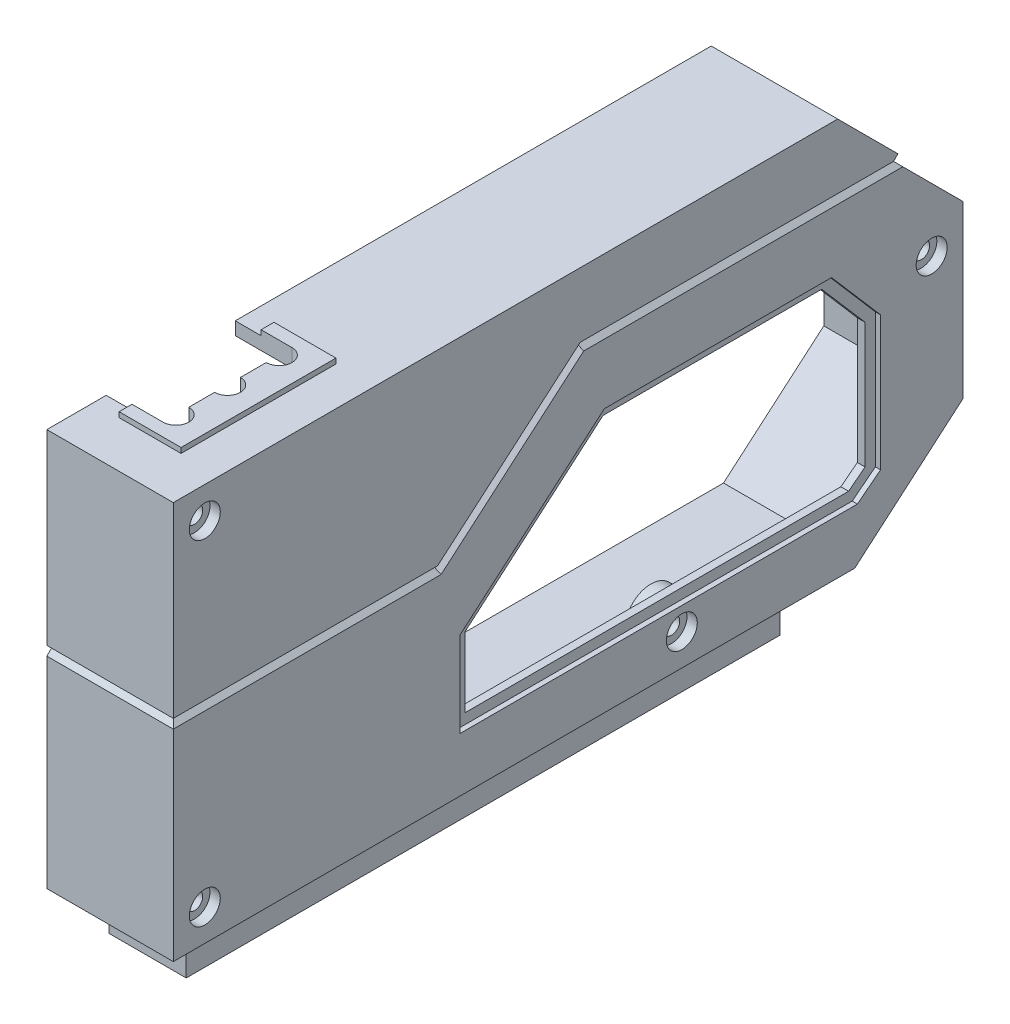
SolidWorks part; units mm, degrees
ref_plane "Front Plane" through (0, 0, 0) normal (0, 0, 1) x (1, 0, 0)
ref_plane "Top Plane" through (0, 0, 0) normal (0, 1, 0) x (1, 0, 0)
ref_plane "Right Plane" through (0, 0, 0) normal (1, 0, 0) x (0, 0, -1)
sketch "Sketch1" plane through (0, 0, 0) normal (1, 0, 0) x (0, 0, -1)
  line L0 (0, 0) -> (0, 77)
  line L1 (0, 77) -> (127, 77)
  line L2 (127, 77) -> (153, 51)
  line L3 (153, 51) -> (153, 18)
  line L4 (153, 18) -> (132, 0)
  line L5 (132, 0) -> (0, 0)
  dimension "D1" = 132
  dimension "D2" = 77
  dimension "D3" = 26
  dimension "D4" = 26
  dimension "D5" = 153
  dimension "D6" = 18
extrude "Base" add sketch "Sketch1" along normal blind 2.5
sketch "Sketch11" plane through (0, 0, 0) normal (-1, 0, 0) x (0, 0, 1)
  line L12 (-131.0752, 2.5) -> (-2.5, 2.5)
  line L13 (-2.5, 2.5) -> (-2.5, 74.5)
  line L14 (-2.5, 74.5) -> (-125.9645, 74.5)
  line L15 (-125.9645, 74.5) -> (-150.5, 49.9645)
  line L16 (-150.5, 49.9645) -> (-150.5, 19.1498)
  line L17 (-150.5, 19.1498) -> (-131.0752, 2.5)
  line L18 (-131.0752, 2.5) -> (-2.5, 2.5)
  line L19 (-2.5, 2.5) -> (-2.5, 74.5)
  line L20 (-2.5, 74.5) -> (-125.9645, 74.5)
  line L21 (-125.9645, 74.5) -> (-150.5, 49.9645)
  line L22 (-150.5, 49.9645) -> (-150.5, 19.1498)
  line L23 (-150.5, 19.1498) -> (-131.0752, 2.5)
  line M7 (-132, 0) -> (0, 0)
  line M8 (0, 0) -> (0, 77)
  line M9 (0, 77) -> (-127, 77)
  line M10 (-127, 77) -> (-153, 51)
  line M11 (-153, 51) -> (-153, 18)
  line M12 (-153, 18) -> (-132, 0)
  dimension "D1" = 2.5
extrude "Boss-Extrude6" add sketch "Sketch11" along normal blind 22 contours L23 L22 L21 L20 L19 L18 M12 M7 M8 M9 M10 M11 region at (0, 10.3005, -141.3853)
ref_plane "Middle" through (-11, 0, 0) normal (1, 0, 0) x (0, 0, -1)
sketch "Sketch17" plane through (0, 77, 0) normal (0, 1, 0) x (1, 0, 0)
  line L5 (-11, -42.35) -> (-11, 42.35) construction
  line L6 (-5, 39) -> (-17, 39)
  line L7 (-5, 39) -> (-5, 9)
  line L8 (-5, 9) -> (-17, 9)
  line L9 (-17, 39) -> (-17, 9)
  line L10 (-5, 39) -> (-17, 9) construction
  line L11 (-5, 9) -> (-17, 39) construction
  line L12 (2.5, 0) -> (-22, 0) construction
  point P0 (-11, 24)
  dimension "D1" = 12
  dimension "D2" = 30
  dimension "D3" = 24
extrude "Boss-Extrude8" add sketch "Sketch17" along normal blind 1
sketch "Sketch13" plane through (0, 78, 0) normal (0, 1, 0) x (1, 0, 0)
  line L0 (-22, 11.5) -> (-11, 11.5)
  line L1 (-22, 0) -> (-22, 127) construction
  line L2 (-11, 16.5) -> (-11, 21.5)
  line L3 (-11, 26.5) -> (-11, 31.5)
  line L4 (-11, 36.5) -> (-22, 36.5)
  line L5 (-22, 36.5) -> (-22, 11.5)
  line L6 (-5, 9) -> (-5, 39) construction
  line L7 (-11, -42.35) -> (-11, 42.35) construction
  arc A0 (-11, 11.5) -> (-11, 16.5) centre (-11, 14) ccw
  arc A1 (-11, 21.5) -> (-11, 26.5) centre (-11, 24) ccw
  arc A2 (-11, 31.5) -> (-11, 36.5) centre (-11, 34) ccw
  point P9 (-5, 24)
  dimension "D1" = 5
  dimension "D4" = 10
  dimension "D5" = 10
extrude "Cut-Extrude2" cut sketch "Sketch13" against normal up to next
sketch "Sketch19" plane through (2.5, 0, 0) normal (1, 0, 0) x (0, 0, -1)
  line L0 (127, 77) -> (128.6971, 77)
  line L1 (128.6971, 77) -> (140.3643, 65.3327)
  line L2 (140.3643, 65.3327) -> (139.5158, 64.4842)
  line L3 (153, 51) -> (127, 77) construction
  line L4 (139.5158, 64.4842) -> (127, 77)
  dimension "D1" = 1.2
  dimension "D2" = 16.5
extrude "Boss-Extrude9" add sketch "Sketch19" against normal up to vertex (24.5 mm away) up to point (-22, 77, -127)
sketch "Sketch20" plane through (0, 102.8485, -102.8485) normal (0, 0.7071, -0.7071) x (-1, 0, 0)
  line L1 (11, 42.35) -> (11, -42.35) construction
  line L2 (2.5, -53.0553) -> (19.5, -53.0553)
  line L3 (2.5, -53.0553) -> (2.5, -44.5553)
  line L4 (2.5, -44.5553) -> (19.5, -44.5553)
  line L5 (19.5, -53.0553) -> (19.5, -44.5553)
  line L6 (2.5, -53.0553) -> (19.5, -44.5553) construction
  line L7 (2.5, -44.5553) -> (19.5, -53.0553) construction
  line L8 (-2.5, -53.0553) -> (-2.5, -36.5553) construction
  line L9 (22, -36.5553) -> (-2.5, -36.5553) construction
  line L10 (22, -53.0553) -> (-2.5, -53.0553) construction
  point P2 (11, -48.8053)
  dimension "D1" = 5
  dimension "D2" = 8
extrude "Cut-Extrude5" cut sketch "Sketch20" against normal up to vertex (1.2 mm away) up to point (2.5, 64.4842, -139.5158)
sketch "Sketch21" plane through (0, 102, -102) normal (0, 0.7071, -0.7071) x (-1, 0, 0)
  line L0 (11, 48.4) -> (11, -48.4) construction
  line L1 (19.5, -44.5553) -> (2.5, -44.5553) construction
  line L2 (11, -48.0053) -> (22, -48.0053)
  line L3 (22, -48.0053) -> (22, -53.1053)
  line L4 (22, -53.0553) -> (22, -72.1249) construction
  line L5 (11, -53.1053) -> (22, -53.1053)
  line L6 (22, 44.5477) -> (22, 46.3155) construction
  arc A0 (11, -48.0053) -> (11, -53.1053) centre (11, -50.5553) ccw
  dimension "D1" = 5.1
  dimension "D2" = 6
extrude "Cut-Extrude6" cut sketch "Sketch21" against normal mid plane 10
sketch "Sketch22" plane through (0, 0, 0) normal (0, -1, 0) x (1, 0, 0)
  line L0 (-11, -42.9) -> (-11, 42.9) construction
  line L1 (-18.5, -8.5) -> (-3.5, -8.5)
  line L2 (-18.5, -8.5) -> (-18.5, -123.5)
  line L3 (-18.5, -123.5) -> (-3.5, -123.5)
  line L4 (-3.5, -8.5) -> (-3.5, -123.5)
  line L5 (-18.5, -8.5) -> (-3.5, -123.5) construction
  line L6 (-18.5, -123.5) -> (-3.5, -8.5) construction
  line L7 (2.5, 0) -> (2.5, -132) construction
  point P0 (-11, -66)
  point P11 (2.5, -66)
  dimension "D1" = 115
  dimension "D2" = 15
extrude "Boss-Extrude10" add sketch "Sketch22" along normal blind 10
sketch "Sketch23" plane through (0, -10, 0) normal (0, -1, 0) x (1, 0, 0)
  line L4 (-18.5, -8.5) -> (-18.5, -123.5) construction
  line L5 (-5.5, -10.5) -> (-16.5, -10.5)
  line L6 (-5.5, -10.5) -> (-5.5, -60.5)
  line L7 (-5.5, -60.5) -> (-16.5, -60.5)
  line L8 (-16.5, -10.5) -> (-16.5, -60.5)
  line L9 (-3.5, -123.5) -> (-3.5, -8.5) construction
  line L10 (-3.5, -8.5) -> (-18.5, -8.5) construction
  dimension "D1" = 2
  dimension "D2" = 2
  dimension "D3" = 2
  dimension "D4" = 50
extrude "Cut-Extrude7" cut sketch "Sketch23" against normal up to next
sketch "Sketch24" plane through (0, -10, 0) normal (0, -1, 0) x (1, 0, 0)
  line L0 (-16.5, -10.5) -> (-16.5, -60.5) construction
  line L1 (-5.5, -60.5) -> (-16.5, -60.5)
  line L2 (-5.5, -60.5) -> (-5.5, -121.5)
  line L3 (-5.5, -121.5) -> (-16.5, -121.5)
  line L4 (-16.5, -60.5) -> (-16.5, -121.5)
  line L5 (-18.5, -123.5) -> (-3.5, -123.5) construction
  dimension "D1" = 2
extrude "Cut-Extrude8" cut sketch "Sketch24" against normal blind 10
sketch "Sketch28" plane through (2.5, 0, 0) normal (1, 0, 0) x (0, 0, -1)
  circle A0 centre (6.1, 70.9) radius 5
  circle A1 centre (146.9, 44.9) radius 5
  circle A2 centre (98.5, 6.1) radius 5
  circle A3 centre (6.1, 6.1) radius 5
  dimension "D9" = 10
  dimension "D1" = 6.1
  dimension "D2" = 6.1
  dimension "D3" = 70.9
  dimension "D4" = 6.1
  dimension "D5" = 98.5
  dimension "D6" = 6.1
  dimension "D7" = 44.9
  dimension "D8" = 146.9
extrude "Boss-Extrude11" add sketch "Sketch28" against normal blind 6
sketch "Sketch29" plane through (2.5, 0, 0) normal (1, 0, 0) x (0, 0, -1)
  circle A0 centre (6.1, 70.9) radius 3
  circle A1 centre (146.9, 44.9) radius 3
  circle A2 centre (98.5, 6.1) radius 3
  circle A3 centre (6.1, 6.1) radius 3
  dimension "D1" = 6
extrude "Cut-Extrude11" cut sketch "Sketch29" against normal blind 2
sketch "Sketch30" plane through (0.5, 0, 0) normal (1, 0, 0) x (0, 0, -1)
  circle A0 centre (6.1, 70.9) radius 1.6
  circle A1 centre (6.1, 6.1) radius 1.6
  circle A2 centre (146.9, 44.9) radius 1.6
  circle A3 centre (98.5, 6.1) radius 1.6
  dimension "D1" = 3.2
extrude "Cut-Extrude12" cut sketch "Sketch30" against normal up to next
sketch "Sketch31" plane through (0, 0, 0) normal (-1, 0, 0) x (0, 0, 1)
  line L1 (-14.5, 47.5) -> (-4.5, 47.5)
  line L2 (-14.5, 47.5) -> (-14.5, 22.5)
  line L3 (-14.5, 22.5) -> (-4.5, 22.5)
  line L4 (-4.5, 47.5) -> (-4.5, 22.5)
  line L5 (-14.5, 47.5) -> (-4.5, 22.5) construction
  line L6 (-14.5, 22.5) -> (-4.5, 47.5) construction
  point P0 (-9.5, 35)
  dimension "D1" = 9.5
  dimension "D2" = 35
  dimension "D3" = 25
  dimension "D4" = 10
extrude "Battery_Support" add sketch "Sketch31" along normal blind 3.4
sketch "Sketch25" plane through (2.5, 0, 0) normal (1, 0, 0) x (0, 0, -1)
  line L0 (55.5, 10.5) -> (132.5, 10.5)
  line L1 (132.5, 10.5) -> (137, 14)
  line L2 (137, 14) -> (137, 40)
  line L3 (137, 40) -> (127.5, 51)
  line L4 (127.5, 51) -> (83.5, 51)
  line L5 (83.5, 51) -> (55.5, 27)
  line L6 (55.5, 27) -> (55.5, 10.5)
  dimension "D1" = 77
  dimension "D2" = 4.5
  dimension "D3" = 3.5
  dimension "D4" = 72
  dimension "D5" = 26
  dimension "D6" = 10.5
  dimension "D7" = 55.5
  dimension "D8" = 40.5
  dimension "D9" = 28
  dimension "D10" = 16.5
extrude "Cut-Extrude9" cut sketch "Sketch25" against normal blind 1
sketch "Sketch26" plane through (1.5, 0, 0) normal (1, 0, 0) x (0, 0, -1)
  line L14 (57.5, 26.0801) -> (57.5, 12.5)
  line L15 (57.5, 12.5) -> (131.8138, 12.5)
  line L16 (131.8138, 12.5) -> (135, 14.9782)
  line L17 (135, 14.9782) -> (135, 39.2559)
  line L18 (135, 39.2559) -> (126.5846, 49)
  line L19 (126.5846, 49) -> (84.2398, 49)
  line L20 (84.2398, 49) -> (57.5, 26.0801)
  line L21 (57.5, 26.0801) -> (57.5, 12.5)
  line L22 (57.5, 12.5) -> (131.8138, 12.5)
  line L23 (131.8138, 12.5) -> (135, 14.9782)
  line L24 (135, 14.9782) -> (135, 39.2559)
  line L25 (135, 39.2559) -> (126.5846, 49)
  line L26 (126.5846, 49) -> (84.2398, 49)
  line L27 (84.2398, 49) -> (57.5, 26.0801)
  dimension "D1" = 2
extrude "Cut-Extrude10" cut sketch "Sketch26" against normal up to next
sketch "Sketch32" plane through (2.5, 0, 0) normal (1, 0, 0) x (0, 0, -1)
  line L0 (144.5158, 63.6842) -> (79.1216, 63.6842)
  line L1 (79.1216, 63.6842) -> (51.49, 40)
  line L2 (51.49, 40) -> (0, 40)
  line L3 (0, 77) -> (0, 0) construction
  line L4 (83.5, 51) -> (55.5, 27) construction
  line L5 (144.5158, 63.6842) -> (144.5158, 64.4842)
  line L6 (144.5158, 64.4842) -> (78.8257, 64.4842)
  line L7 (78.8257, 64.4842) -> (51.1941, 40.8)
  line L8 (51.1941, 40.8) -> (0, 40.8)
  line L9 (0, 40.8) -> (0, 40)
  dimension "D1" = 0.8
  dimension "D2" = 0.8
  dimension "D3" = 0.8
  dimension "D4" = 5
  dimension "D5" = 12.48
  dimension "D6" = 40
extrude "Cut-Extrude13" cut sketch "Sketch32" against normal blind 1
sketch "Sketch33" plane through (0, 0, 0) normal (0, 0, 1) x (1, 0, 0)
  line L0 (-22, 0) -> (-22, 77) construction
  line L1 (1.5, 40.8) -> (-22, 40.8)
  line L2 (1.5, 40.8) -> (1.5, 40)
  line L3 (1.5, 40) -> (-22, 40)
  line L4 (-22, 40.8) -> (-22, 40)
  point P7 (1.5, 40)
extrude "Cut-Extrude14" cut sketch "Sketch33" against normal blind 1
chamfer "Chamfer1" distance 1 angle 45 4 edges at (-9.75, 40, 0) (2.5, 40, -25.745) (2.5, 51.8421, -65.3058) (2.5, 63.6842, -109.7187)
equation "\"D5@Sketch13\"=\"D4@Sketch13\""
equation "\"D2@Sketch23\"=\"D1@Sketch23\""
equation "\"D3@Sketch23\"=\"D1@Sketch23\""
equation "\"D2@Sketch32\"=\"D1@Sketch32\""
equation "\"D3@Sketch32\"=\"D1@Sketch32\""
